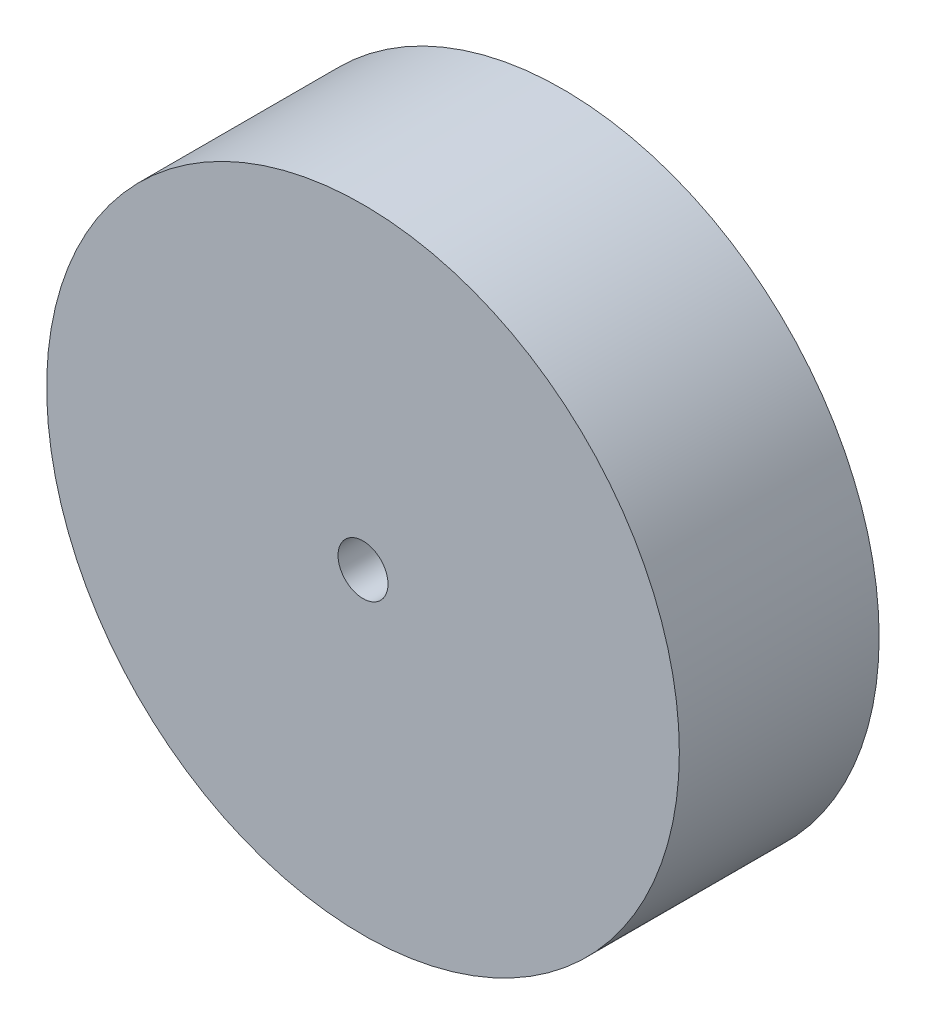
SolidWorks part; units mm, degrees
ref_plane "前视基准面" through (0, 0, 0) normal (0, 0, 1) x (1, 0, 0)
ref_plane "上视基准面" through (0, 0, 0) normal (0, 1, 0) x (1, 0, 0)
ref_plane "右视基准面" through (0, 0, 0) normal (1, 0, 0) x (0, 0, -1)
other "Configuration Table"
sketch "草图1" plane through (0, 0, 0) normal (0, 0, 1) x (1, 0, 0)
  circle A0 centre (0, 0) radius 38
  circle A1 centre (0, 0) radius 3
  dimension "D1" = 76
extrude "凸台-拉伸1" add sketch "草图1" along normal blind 24
